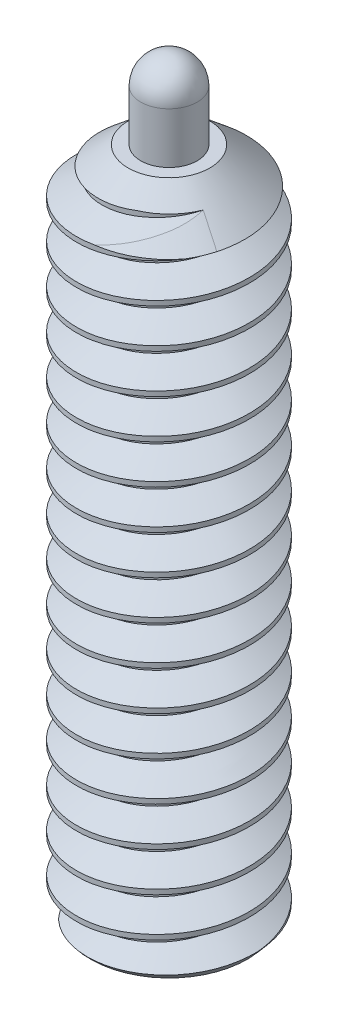
SolidWorks part; units mm, degrees
ref_plane "Front" through (0, 0, 0) normal (0, 0, 1) x (1, 0, 0)
ref_plane "Top" through (0, 0, 0) normal (0, 1, 0) x (1, 0, 0)
ref_plane "Right" through (0, 0, 0) normal (1, 0, 0) x (0, 0, -1)
sketch "Sketch24" plane through (0, 0, 0) normal (1, 0, 0) x (0, 0, -1)
  line L0 (1.7526, 6.7437) -> (-1.7526, 6.7437) construction
  line L1 (0, 6.7437) -> (1.7526, 6.7437)
  line L2 (0, 6.7437) -> (0, -6.7437)
  line L3 (0, -6.7437) -> (1.7526, -6.7437)
  line L4 (1.7526, 6.7437) -> (1.7526, -6.7437)
  point P5 (1.7526, 3.1718)
  dimension "Body Length" = 13.4874
  dimension "Screw Dia" = 3.5052
  dimension "D1" = 3.5719
revolve "Revolve1" add sketch "Sketch24" angle 360 about L2
sketch "Sketch37" plane through (0, 6.7437, 0) normal (0, 1, 0) x (1, 0, 0)
  circle A1 centre (0, 0) radius 1.7526
  circle A2 centre (0, 0) radius 1.7526
  dimension "D1" = 0
curve "Helix/Spiral1" pitch 0.7937 height 14.2812 turns 17.992 parameters "pitch"=0.7937
sketch "Sketch38" plane through (0, 0, 0) normal (1, 0, 0) x (0, 0, -1)
  line L0 (-1.7526, 7.4382) -> (-1.7526, 6.7437)
  line L1 (-1.7526, 7.4382) -> (-1.237, 7.1406)
  line L2 (-1.237, 7.1406) -> (-1.237, 7.0414)
  line L3 (-1.237, 7.0414) -> (-1.7526, 6.7437)
  line L4 (-1.237, 7.091) -> (-1.7526, 7.091) construction
  line L5 (-1.4948, 7.2894) -> (-1.4948, 6.8925) construction
  line L6 (1.7526, 6.7437) -> (-1.7526, 6.7437) construction
  line L7 (0, 0) -> (0, 6.7437) construction
  dimension "D1" = 0.0992
  dimension "D2" = 0.3969
  dimension "D3" = 60
  dimension "D4" = 0.5156
  dimension "D5" = 1.237
sweep "Cut-Sweep1" cut profiles "Sketch38" path "Helix/Spiral1" align with end faces yes
sketch "Sketch26" plane through (0, 0, 0) normal (1, 0, 0) x (0, 0, -1)
  line L0 (0, -5.4737) -> (0, 6.7437)
  line L1 (0, 6.7437) -> (0, -6.7437) construction
  line L2 (0, 6.7437) -> (0.5715, 6.7437)
  line L3 (0.5715, 6.7437) -> (0.5715, -5.4737)
  line L5 (0.5715, -5.4737) -> (0, -5.4737)
  line L7 (0.5715, 6.7437) -> (-0.5715, 6.7437) construction
  line L8 (1.7526, 6.7437) -> (-1.7526, 6.7437) construction
  dimension "D1" = 1.27
  dimension "Ball Dia" = 1.143
revolve "Cut-Revolve10" cut sketch "Sketch26" angle 360 about L0
sketch "Sketch31" plane through (0, 0, 0) normal (1, 0, 0) x (0, 0, -1)
  line L0 (1.7526, -6.7437) -> (1.5875, -6.7437)
  line L1 (1.7526, 6.7437) -> (1.7526, -6.7437) construction
  line L3 (0, 0) -> (0, -14.5366) construction
  line L4 (1.5875, -6.7437) -> (1.7526, -6.5469)
  line L5 (0, 0) -> (1.7526, 0) construction
  line L14 (1.7526, 6.7437) -> (0.8255, 6.7437)
  line L15 (0, 6.7437) -> (1.7526, 6.7437) construction
  line L16 (0.8255, 6.7437) -> (1.7526, 5.9658)
  line L17 (1.7526, 5.9658) -> (1.7526, 6.7437)
  line L18 (1.7526, -6.5469) -> (1.7526, -6.7437)
  dimension "D1" = 0.254
  dimension "D2" = 40
  dimension "D3" = 0.762
revolve "Cut-Revolve13" cut sketch "Sketch31" angle 360 about L2
sketch "Sketch27" plane through (0, 0, 0) normal (1, 0, 0) x (0, 0, -1)
  line L0 (0, 6.7437) -> (0, -6.7437) construction
  line L1 (0.5715, 6.7437) -> (0.5715, -5.4737) construction
  line L2 (0, -6.7437) -> (0, 7.2009) construction
  line L3 (0, 8.3439) -> (0, 0.635)
  line L4 (0.5715, 7.7724) -> (0.5715, 0.635)
  line L5 (0.5715, 0.635) -> (0, 0.635)
  circle A0 centre (0, 7.7724) radius 0.5715 construction
  arc A1 (0, 8.3439) -> (0.5715, 7.7724) centre (0, 7.7724) cw
  point P15 (0.5715, 0.635)
  dimension "D1" = 1.143
  dimension "Ball Projection" = 1.6002
revolve "Revolve2" add sketch "Sketch27" angle 360 about L3
ref_plane "Plane1" [suppressed] through (-3.175, 0, 0) normal (1, 0, 0) x (0, 0, -1)
sketch "Sketch21" [suppressed] plane through (-3.175, 0, 0) normal (1, 0, 0) x (0, 0, -1)
  line L0 (0, -1.7183) -> (0, -3.2804) construction
  line L2 (3.175, 12.7) -> (-3.175, 12.7) construction
  line L3 (0, 12.7) -> (0, -12.7) construction
  ellipse E0 centre (0, 7.351) end of major axis (0, 9.4147) minor radius 1.5875
  dimension "D5" = 1.7526
  dimension "D6" = 2.2784
  dimension "D7" = 2.8746
sketch "Sketch41" [suppressed] plane through (-3.175, 0, 0) normal (1, 0, 0) x (0, 0, -1)
  ellipse E1 centre (0, 7.351) end of major axis (0, 9.4147) minor radius 1.5875
  ellipse E2 centre (0, 7.351) end of major axis (0, 9.4147) minor radius 1.5875
  dimension "D1" = 0
sketch "Sketch43" [suppressed] plane through (0, 0, 0) normal (1, 0, 0) x (0, 0, -1)
  ellipse E1 centre (0, 7.351) end of major axis (0, 9.4147) minor radius 1.5875
  ellipse E2 centre (0, 7.351) end of major axis (0, 9.4147) minor radius 1.5875
  dimension "D1" = 0
extrude "Extrude9" [suppressed] cut sketch "Sketch43" against normal blind 76.2
sketch "Sketch44" [suppressed] plane through (0, 0, 0) normal (1, 0, 0) x (0, 0, -1)
  ellipse E1 centre (0, 7.351) end of major axis (0, 9.4147) minor radius 1.5875
  ellipse E2 centre (0, 7.351) end of major axis (0, 9.4147) minor radius 1.5875
  dimension "D1" = 0
extrude "Extrude10" [suppressed] add sketch "Sketch44" against normal blind 1.237 separate body
dome "Dome1" [suppressed] faces to dome 1 distance 0.2578 parameters "D1"=0.2578
sketch "Sketch45" plane through (0, 0, 0) normal (0, 1, 0) x (1, 0, 0)
  circle A0 centre (0, 0) radius 0.5715
  circle A1 centre (0, 0) radius 0.5715 construction
extrude "Extrude11" [suppressed] cut sketch "Sketch45" against normal through all and the other way through all
sketch "Sketch46" plane through (0, -6.7437, 0) normal (0, -1, 0) x (1, 0, 0)
  line L1 (-0.635, 0.3666) -> (-0.635, -0.3666)
  line L2 (-0.635, -0.3666) -> (0, -0.7332)
  line L3 (0, -0.7332) -> (0.635, -0.3666)
  line L4 (0.635, -0.3666) -> (0.635, 0.3666)
  line L5 (0.635, 0.3666) -> (0, 0.7332)
  line L6 (0, 0.7332) -> (-0.635, 0.3666)
  circle A0 centre (0, 0) radius 0.635 construction
  dimension "Hex" = 1.27
extrude "Extrude12" cut sketch "Sketch46" against normal blind 0.635
sketch "Sketch47" plane through (0, -6.7437, 0) normal (0, -1, 0) x (1, 0, 0)
  circle A0 centre (0, 0) radius 0.7332
extrude "Extrude13" cut sketch "Sketch47" against normal blind 0.635 draft 60
equation "\"D1@Sketch26\" = \"Hex@Sketch46\""
equation "\"D1@Sketch38\" = \"pitch@Helix/Spiral1\"*.125"
equation "\"D2@Sketch38\" = \"pitch@Helix/Spiral1\"*.50"
equation "\"D3@Helix/Spiral1\" = \"Body Length@Sketch24\"+\"pitch@Helix/Spiral1\""
equation "\"D5@Sketch21\" = \"Screw Dia@Sketch24\"*.50"
equation "\"D6@Sketch21\" = \"D5@Sketch21\"*1.3"
equation "\"D7@Sketch21\" = \"pitch@Helix/Spiral1\"*3.62154"
equation "\"D1@Sketch24\" = \"pitch@Helix/Spiral1\"*4.50"
equation "\"D1@Plane1\" = \"Screw Dia@Sketch24\"/2"
equation "\"D1@Extrude10\" = \"D5@Sketch38\""
equation "\"D1@Dome1\" = \"D6@Sketch38\""
equation "\"D1@Extrude12\" = \"Hex@Sketch46\"/2"
equation "\"D1@Extrude13\" = \"Hex@Sketch46\"/2"
